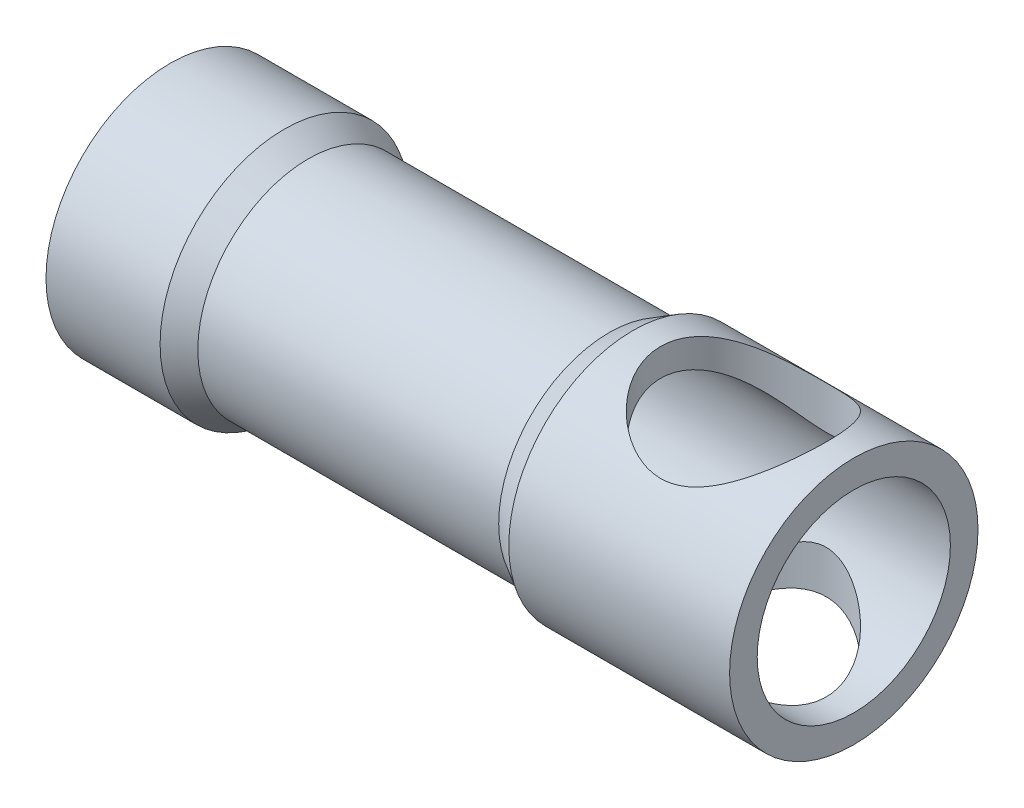
SolidWorks part; units mm, degrees
ref_plane "Front Plane" through (0, 0, 0) normal (0, 0, 1) x (1, 0, 0)
ref_plane "Top Plane" through (0, 0, 0) normal (0, 1, 0) x (1, 0, 0)
ref_plane "Right Plane" through (0, 0, 0) normal (1, 0, 0) x (0, 0, -1)
sketch "Sketch1" plane through (0, 0, 0) normal (0, 0, 1) x (1, 0, 0)
  line L0 (0, 0) -> (43.7471, 0) construction
  line L1 (0, 6) -> (0, 14.2875)
  line L2 (0, 14.2875) -> (13.1254, 14.2875)
  line L3 (78.6384, 14.2875) -> (78.6384, 11.1125)
  line L4 (78.6384, 11.1125) -> (15.875, 11.1125)
  line L5 (13.1254, 14.2875) -> (15.875, 12.7)
  line L8 (15.875, 11.1125) -> (15.875, 6)
  line L9 (15.875, 6) -> (0, 6)
  line L10 (15.875, 12.7) -> (50.4888, 12.7)
  line L11 (50.4888, 12.7) -> (53.2384, 14.2875)
  line L12 (15.875, 11.1125) -> (15.875, 12.7) construction
  line L13 (53.2384, 14.2875) -> (78.6384, 14.2875)
  point P12 (52.1477, 12.3983)
  point P14 (0, 0)
  dimension "D1" = 6
  dimension "D2" = 14.2875
  dimension "D3" = 15.875
  dimension "D4" = 78.6384
  dimension "D5" = 25.4
  dimension "D6" = 30
  dimension "D7" = 30
  dimension "D8" = 1.5875
  dimension "D9" = 3.175
revolve "Revolve1" add sketch "Sketch1" angle 360 about L0
thread "Thread1" pitch 1.5 method cut profile "Thread Profile1" start angle 0, offset 0, length 19.05, pitch 1.5, diameter 12
ref_plane "Plane1" through (0, 0, -6) normal (0, -1, 0) x (0, 0, -1)
sketch "Thread Profile1" plane through (0, 0, -6) normal (0, -1, 0) x (0, 0, -1)
  line L0 (0, 0) -> (0, 1.5) construction
  line L1 (0, 0) -> (0.8119, 0.4687)
  line L2 (0.8119, 0.4687) -> (0.8119, 0.6562)
  line L3 (0.8119, 0.6562) -> (0, 1.125)
  line L4 (0.8119, 0.5625) -> (0, 0.5625) construction
  line L11 (0, 0) -> (0, 1.125)
  point P2 (0, 0)
  dimension "Pitch" = 1.5
  dimension "Profile_Angle" = 60
  dimension "Profile_Land" = 0.1875
  dimension "Profile_Height" = 0.8119
sketch "Sketch4" plane through (0, 0, 0) normal (0, 1, 0) x (1, 0, 0)
  line L0 (0, 0) -> (78.6384, 0) construction
  line L1 (0, 14.2875) -> (0, -14.2875) construction
  line L2 (78.6384, -14.2875) -> (78.6384, 14.2875) construction
  line L3 (65.9384, 0) -> (78.6384, 0) construction
  circle A0 centre (65.9384, 0) radius 9.525
  dimension "D1" = 19.05
  dimension "D2" = 12.7
extrude "Cut-Extrude1" cut sketch "Sketch4" against normal mid plane 50.8
